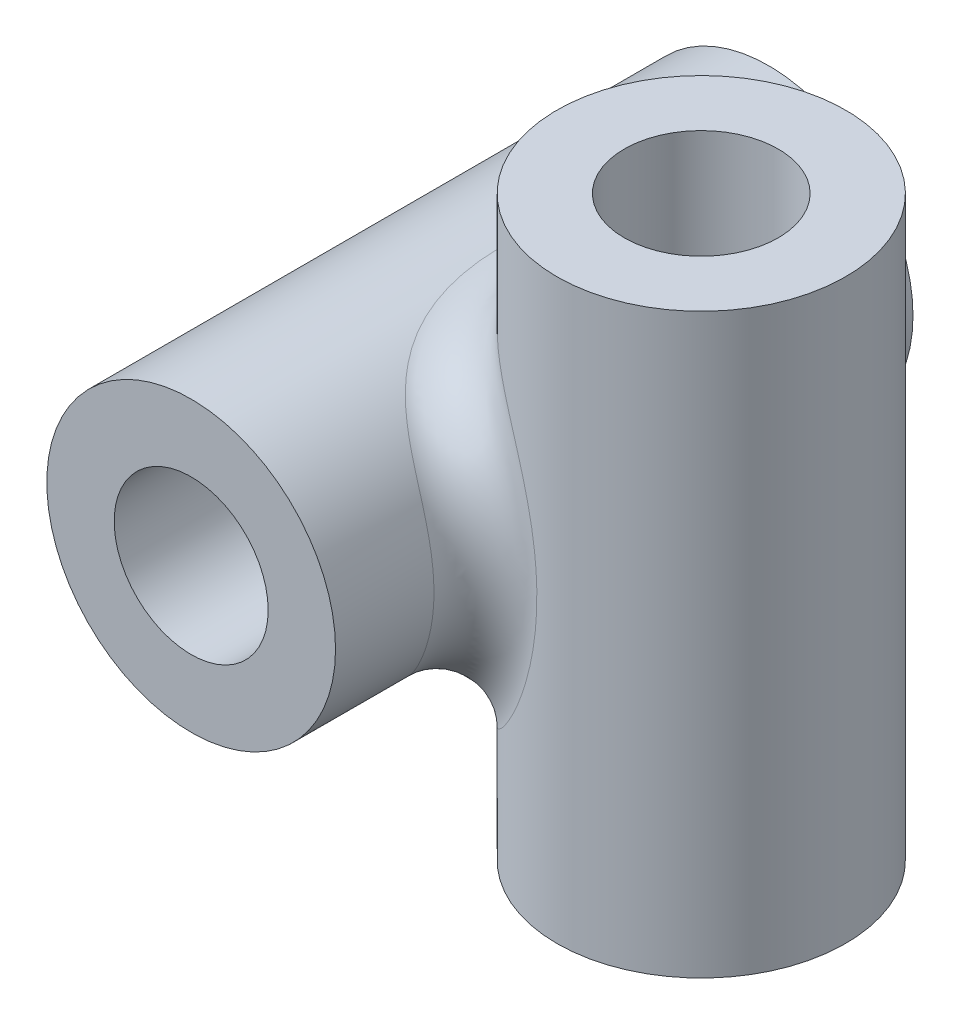
SolidWorks part; units mm, degrees
ref_plane "Front Plane" through (0, 0, 0) normal (0, 0, 1) x (1, 0, 0)
ref_plane "Top Plane" through (0, 0, 0) normal (0, 1, 0) x (1, 0, 0)
ref_plane "Right Plane" through (0, 0, 0) normal (1, 0, 0) x (0, 0, -1)
sketch "Sketch1" plane through (0, 0, 0) normal (0, 0, 1) x (1, 0, 0)
  circle A0 centre (0, 0) radius 8
  circle A1 centre (0, 0) radius 15
  dimension "D1" = 16
  dimension "D2" = 30
extrude "Boss-Extrude1" add sketch "Sketch1" along normal blind 60
ref_plane "Plane2" through (0, 15, 0) normal (0, 1, 0) x (1, 0, 0)
sketch "Sketch2" plane through (0, 15, 0) normal (0, 1, 0) x (1, 0, 0)
  line L0 (15, -30) -> (-49985, -30) construction
  line L1 (15, -60) -> (15, 0) construction
  line L2 (15, -30) -> (15, 49970) construction
  line L3 (-15, 0) -> (-15, -60) construction
  circle A0 centre (23, -30) radius 8
  circle A1 centre (23, -30) radius 15
  point P4 (15, -30)
  dimension "D2" = 30
  dimension "D3" = 16
  dimension "D1" = 38
sketch "Sketch3" plane through (0, 0, 0) normal (0, 1, 0) x (1, 0, 0)
  circle A0 centre (23, -30) radius 15 construction
  circle A1 centre (23, -30) radius 8 construction
  circle A2 centre (23, -30) radius 15
  circle A3 centre (23, -30) radius 8
extrude "Boss-Extrude2" add sketch "Sketch3" along normal mid plane 60
fillet "Fillet1" radius 5 1 edges at (14.6137, 3.3823, 17.5634)
